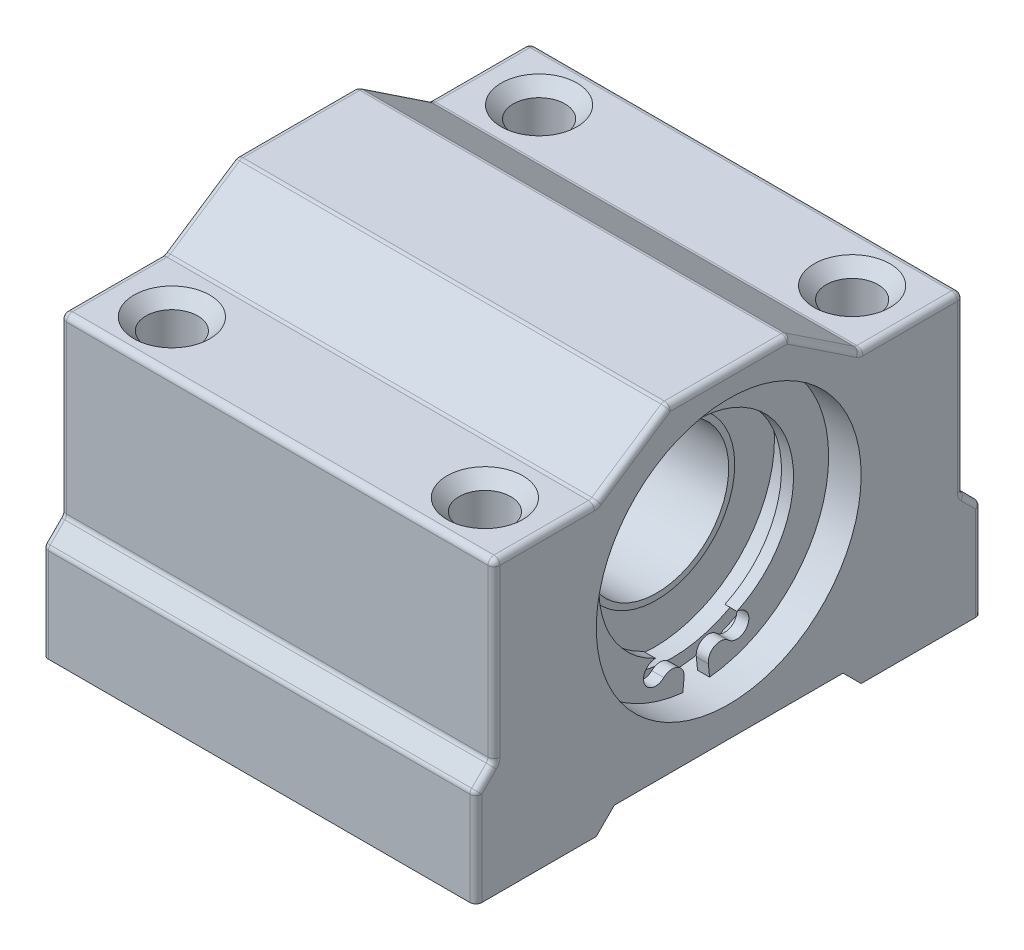
SolidWorks part; units mm, degrees
ref_plane "Front Plane" through (0, 0, 0) normal (0, 0, 1) x (1, 0, 0)
ref_plane "Top Plane" through (0, 0, 0) normal (0, 1, 0) x (1, 0, 0)
ref_plane "Right Plane" through (0, 0, 0) normal (1, 0, 0) x (0, 0, -1)
sketch "Sketch1" plane through (0, 0, 0) normal (1, 0, 0) x (0, 0, -1)
  line L1 (-11, -15) -> (-9.5, -13.5)
  line L2 (-9.5, -13.5) -> (9.5, -13.5)
  line L3 (9.5, -13.5) -> (11, -15)
  line L4 (11, -15) -> (21, -15)
  line L6 (21, -7) -> (19.5, -5.5)
  line L8 (19.5, 9) -> (11, 9)
  line L9 (11, 9) -> (5, 13)
  line L10 (5, 13) -> (-5, 13)
  line L11 (-5, 13) -> (-11, 9)
  line L12 (-11, 9) -> (-19.5, 9)
  line L15 (-21, -7) -> (-21, -15)
  line L16 (0, -13.5) -> (0, 13) construction
  line L17 (-16.278, 0) -> (14.0247, 0) construction
  line L18 (-21, -15) -> (-11, -15)
  line L19 (21, -7) -> (21, -15)
  line L20 (-19.5, -5.5) -> (-19.5, 9)
  line L21 (19.5, -5.5) -> (19.5, 9)
  line L22 (-15.25, 9) -> (-15.25, -15) construction
  line L23 (-15.25, -15) -> (15.25, 9) construction
  line L24 (15.25, 9) -> (15.25, -15) construction
  line L25 (-21, -7) -> (-19.5, -5.5)
  line L26 (-11, 0) -> (11, 0) construction
  circle A0 centre (0, 0) radius 11
  circle A1 centre (0, 0) radius 10
  circle A2 centre (0, 0) radius 6
  point P18 (0, 13)
  dimension "D12" = 12
  dimension "D1" = 42
  dimension "D2" = 24
  dimension "D3" = 15
  dimension "D5" = 28
  dimension "D6" = 30.5
  dimension "D4" = 8
  dimension "D7" = 1.5
  dimension "D8" = 10
  dimension "D9" = 1.5
  dimension "D10" = 10
  dimension "D11" = 1
extrude "Boss-Extrude1" add sketch "Sketch1" along normal blind 36 contours L25 L15 L18 L1 L2 L3 L4 L19 L6 L21 L8 L9 L10 L11 L12 L20 A0 region at (0, -14.4952, 16)
extrude "Extrude-Thin1" add sketch "Sketch1<4>" along normal blind 29.5 from offset 0.5 separate body thin contours A2 thin type one direction wall 0.5
sketch "Sketch1<4>" plane through (0, 0, 0) normal (1, 0, 0) x (0, 0, -1) same geometry as "Sketch1"
extrude "Boss-Extrude2" add sketch "Sketch1<5>" along normal blind 29 from offset 0.8 contours A1 A2 region at (0, 0, 9.7172)
sketch "Sketch1<5>" plane through (0, 0, 0) normal (1, 0, 0) x (0, 0, -1) same geometry as "Sketch1"
extrude "Boss-Extrude3" add sketch "Sketch1<6>" along normal blind 31 from offset 0.3 contours A0 A1 region at (0, 0, 10.6889)
sketch "Sketch1<6>" plane through (0, 0, 0) normal (1, 0, 0) x (0, 0, -1) same geometry as "Sketch1"
ref_plane "Plane1" through (31.3, 0, 0) normal (1, 0, 0) x (0, 0, -1)
sketch "Sketch3" plane through (31.3, 0, 0) normal (1, 0, 0) x (0, 0, -1)
  line L0 (0, 0) -> (0, -50000) construction
  line L1 (-1.0114, -9.9487) -> (-1.1126, -10.9436)
  line L2 (1.0114, -9.9487) -> (1.1126, -10.9436)
  circle A0 centre (0, 0) radius 11 construction
  arc A1 (1.1126, -10.9436) -> (-1.1126, -10.9436) centre (0, 0) ccw
  circle A2 centre (0, 0) radius 10 construction
  arc A3 (0, -10) -> (1.0114, -9.9487) centre (0, 0) ccw
  arc A4 (-1.0114, -9.9487) -> (-2.6866, -9.0709) centre (-2, -9.798) ccw
  circle A5 centre (-2, -9.798) radius 0.25
  arc A6 (-2.2443, -9.7449) -> (-1.7544, -9.8449) centre (0, 0) ccw
  arc A7 (-2.6866, -9.0709) -> (-3.3785, -7.3439) centre (-3.3732, -8.3439) cw
  arc A8 (2.6866, -9.0709) -> (3.3785, -7.3439) centre (3.3732, -8.3439) ccw
  circle A10 centre (2, -9.798) radius 0.25
  arc A11 (1.0114, -9.9487) -> (2.6866, -9.0709) centre (2, -9.798) cw
  arc A13 (3.3785, -7.3439) -> (-3.3785, -7.3439) centre (0, 0) ccw
  dimension "D1" = 0.5
  dimension "D2" = 2
  dimension "D3" = 1
  dimension "D4" = 2
extrude "Boss-Extrude4" add sketch "Sketch3" along normal blind 1 from offset 1 contours A11 A8 A13 A7 A4 L1 A1 L2
fillet "Fillet1" radius 0.5 32 edges at (18, -5.5, -19.5) (18, -5.5, 19.5) (18, -7, 21) (18, -7, -21) (18, 9, -11) (18, 9, 11) (18, 13, 5) (18, 13, -5) (18, 9, -19.5) (18, 9, 19.5) (36, 11, -8) (36, 11, 8) (36, 1.75, 19.5) (0, -6.25, 20.25) (0, 11, 8) (36, -6.25, -20.25) (36, -11, -21) (36, 1.75, -19.5) (36, 13, 0) (36, 9, -15.25) (36, 9, 15.25) (36, -6.25, 20.25) (36, -11, 21) (0, -11, -21) (0, -6.25, -20.25) (0, 1.75, -19.5) (0, 11, -8) (0, 9, -15.25) (0, 13, 0) (0, -11, 21) (0, 1.75, 19.5) (0, 9, 15.25)
sketch "Sketch4" plane through (0, -15, 0) normal (0, -1, 0) x (1, 0, 0)
  line L0 (18, 21) -> (18, -21) construction
  line L1 (35.5, 21) -> (0.5, 21) construction
  line L2 (35.5, -21) -> (0.5, -21) construction
  line L4 (-4.9444, 15.25) -> (27.0918, 15.25) construction
  line L6 (0, 0) -> (36.1646, 0) construction
  circle A0 centre (5, 15.25) radius 2.15
  circle A1 centre (31, 15.25) radius 2.15
  circle A2 centre (31, -15.25) radius 2.15
  circle A3 centre (5, -15.25) radius 2.15
  dimension "D2" = 4.3
  dimension "D1" = 15.25
  dimension "D3" = 26
extrude "Cut-Extrude3" cut sketch "Sketch4" against normal through all
chamfer "Chamfer1" distance 1 angle 45 8 edges at (31, 9, -17.4) (5, 9, -17.4) (5, 9, 13.1) (31, 9, 13.1) (31, -15, 17.4) (5, -15, 13.1) (31, -15, -17.4) (5, -15, -13.1)
ref_plane "Plane2" through (5, 0, 0) normal (-1, 0, 0) x (0, 0, 1)
ref_plane "Plane3" through (31, 0, 0) normal (1, 0, 0) x (0, 0, -1)
equation "\"D1@Boss-Extrude2\"= \"D1@Boss-Extrude1\" - 2 - 5"
equation "\"D1@Boss-Extrude3\"= \"D1@Boss-Extrude1\" - 5"
equation "\"D1@Sketch4\"= \"D6@Sketch1\" / 2"
equation "\"D1@Extrude-Thin1\"= \"D1@Boss-Extrude3\" - 1.5"
